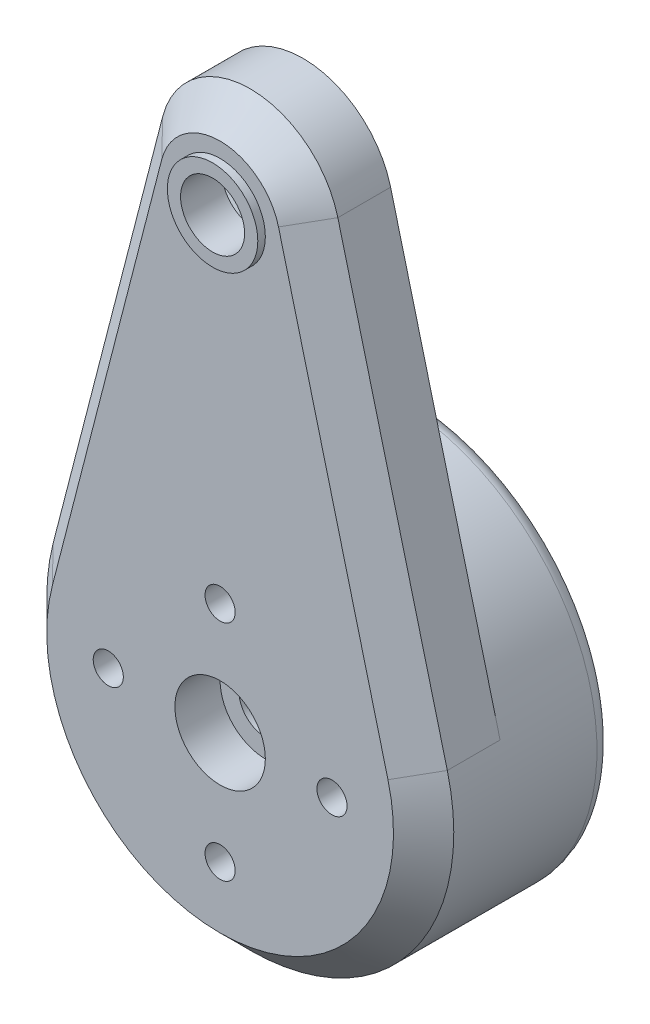
SolidWorks part; units mm, degrees
ref_plane "Front Plane" through (0, 0, 0) normal (0, 0, 1) x (1, 0, 0)
ref_plane "Top Plane" through (0, 0, 0) normal (0, 1, 0) x (1, 0, 0)
ref_plane "Right Plane" through (0, 0, 0) normal (1, 0, 0) x (0, 0, -1)
sketch "Sketch1" plane through (0, 0, 0) normal (0, 0, 1) x (1, 0, 0)
  line L0 (0, 0) -> (0, 30) construction
  line L1 (-13.0713, 3.375) -> (-5.8095, 31.5)
  line L2 (5.8095, 31.5) -> (13.0713, 3.375)
  arc A0 (-13.0713, 3.375) -> (13.0713, 3.375) centre (0, 0) ccw
  arc A1 (5.8095, 31.5) -> (-5.8095, 31.5) centre (0, 30) ccw
  circle A2 centre (0, 30) radius 2.125
  circle A3 centre (0, 0) radius 10
  circle A4 centre (0, 0) radius 1.625
  dimension "D1" = 27
  dimension "D3" = 12
  dimension "D4" = 4.25
  dimension "D5" = 20
  dimension "D6" = 3.25
  dimension "D2" = 30
extrude "Boss-Extrude1" add sketch "Sketch1" along normal blind 5.5 contours A3 | L2 A1 L1 A0 A3 A2 | A4 region at (0, 12.4311, 0) region at (-9.7172, 0, 0) region at (0, 0, 0)
sketch "Sketch4" plane through (0, 0, 0) normal (0, 0, -1) x (-1, 0, 0)
  circle A4 centre (0, 0) radius 13.5
  arc A5 (-13.0713, 3.375) -> (13.0713, 3.375) centre (0, 0) ccw construction
extrude "Boss-Extrude2" add sketch "Sketch4" along normal blind 7
sketch "Sketch6" plane through (0, 0, -7) normal (0, 0, -1) x (-1, 0, 0)
  circle A0 centre (0, 0) radius 11
  dimension "D1" = 22
extrude "Cut-Extrude4" cut sketch "Sketch6" against normal blind 4
sketch "Sketch5" plane through (0, 0, -3) normal (0, 0, -1) x (-1, 0, 0)
  line L0 (0, 0) -> (7.42, 0) construction
  circle A0 centre (7.42, 0) radius 1
  circle A1 centre (0, -7.42) radius 1
  circle A2 centre (-7.42, 0) radius 1
  circle A3 centre (0, 7.42) radius 1
  circle A4 centre (0, 0) radius 7.42 construction
  circle A5 centre (0, 0) radius 1.75
  point P12 (0, 0)
  dimension "D2" = 2
  dimension "D1" = 14.84
  dimension "D4" = 3.5
  dimension "D3" = 4
extrude "Cut-Extrude2" cut sketch "Sketch5" against normal through all
chamfer "Chamfer1" distance 2 angle 45 4 edges at (0, -13.5, 5.5) (-9.4404, 17.4375, 5.5) (0, 36, 5.5) (9.4404, 17.4375, 5.5)
sketch "Sketch7" plane through (0, 0, 5.5) normal (0, 0, 1) x (1, 0, 0)
  circle A0 centre (0, 0) radius 3
  dimension "D1" = 6
extrude "Cut-Extrude5" cut sketch "Sketch7" against normal blind 3
fillet "Fillet1" radius 1 1 edges at (-13.5, 0, -7)
sketch "Sketch8" plane through (0, 0, 5.5) normal (0, 0, 1) x (1, 0, 0)
  circle A0 centre (0, 30) radius 3
  circle A2 centre (0, 30) radius 2.125 construction
  circle A3 centre (0, 30) radius 2.125
  dimension "D1" = 6
extrude "Boss-Extrude3" add sketch "Sketch8" along normal blind 0.5
sketch "Sketch9" plane through (0, 0, 0) normal (0, 0, -1) x (-1, 0, 0)
  line L1 (0, 25.6699) -> (3.75, 27.8349)
  line L2 (3.75, 27.8349) -> (3.75, 32.1651)
  line L3 (3.75, 32.1651) -> (0, 34.3301)
  line L4 (0, 34.3301) -> (-3.75, 32.1651)
  line L5 (-3.75, 32.1651) -> (-3.75, 27.8349)
  line L6 (-3.75, 27.8349) -> (0, 25.6699)
  circle A0 centre (0, 30) radius 3.75 construction
  dimension "D1" = 7.5
extrude "Cut-Extrude6" cut sketch "Sketch9" against normal blind 3.25
fillet "Fillet2" radius 0.5 6 edges at (3.75, 30, 0) (1.875, 26.7524, 0) (-1.875, 26.7524, 0) (-3.75, 30, 0) (-1.875, 33.2476, 0) (1.875, 33.2476, 0)
